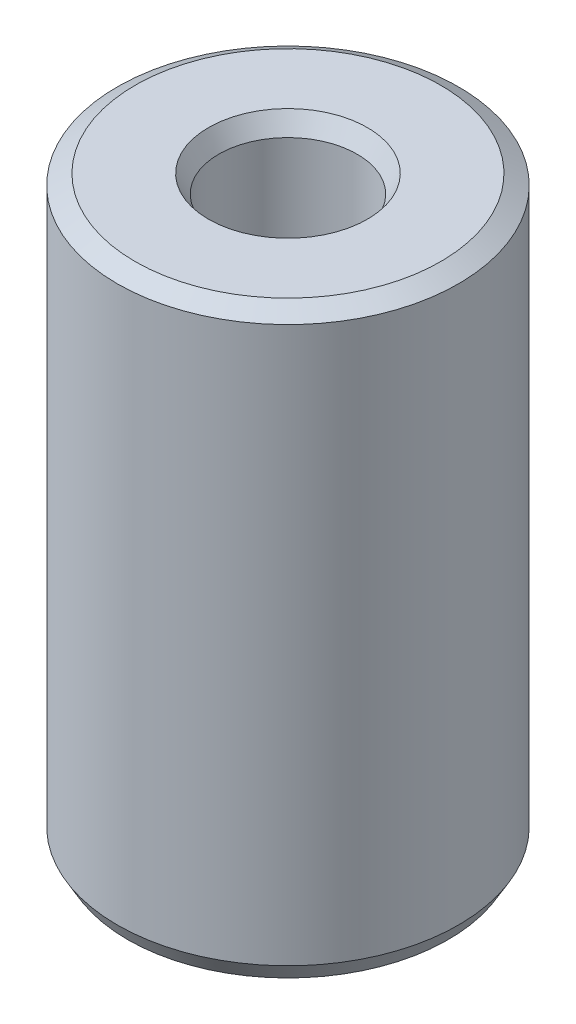
SolidWorks part; units mm, degrees
ref_plane "Front Plane" through (0, 0, 0) normal (0, 0, 1) x (1, 0, 0)
ref_plane "Top Plane" through (0, 0, 0) normal (0, 1, 0) x (1, 0, 0)
ref_plane "Right Plane" through (0, 0, 0) normal (1, 0, 0) x (0, 0, -1)
sketch "Sketch1" plane through (0, 0, 0) normal (0, 1, 0) x (1, 0, 0)
  circle A0 centre (0, 0) radius 27.5
  dimension "SLEEVE_OD" = 55
extrude "Boss-Extrude1" add sketch "Sketch1" along normal blind 94.0402
sketch "Sketch2" plane through (0, 0, 0) normal (0, 1, 0) x (1, 0, 0)
  circle A0 centre (0, 0) radius 11.1452
  dimension "BORE_D" = 22.2904
extrude "Cut-Extrude1" cut sketch "Sketch2" along normal through all
chamfer "Chamfer1" distance 1.6608 angle 60 4 edges at (0, 94.0402, 11.1452) (0, 0, 11.1452) (0, 0, 27.5) (0, 94.0402, 27.5) first distance on face at (0, 94.0402, 11.1452) first distance on face at (0, 0, 11.1452) first distance on face at (0, 94.0402, 27.5)
